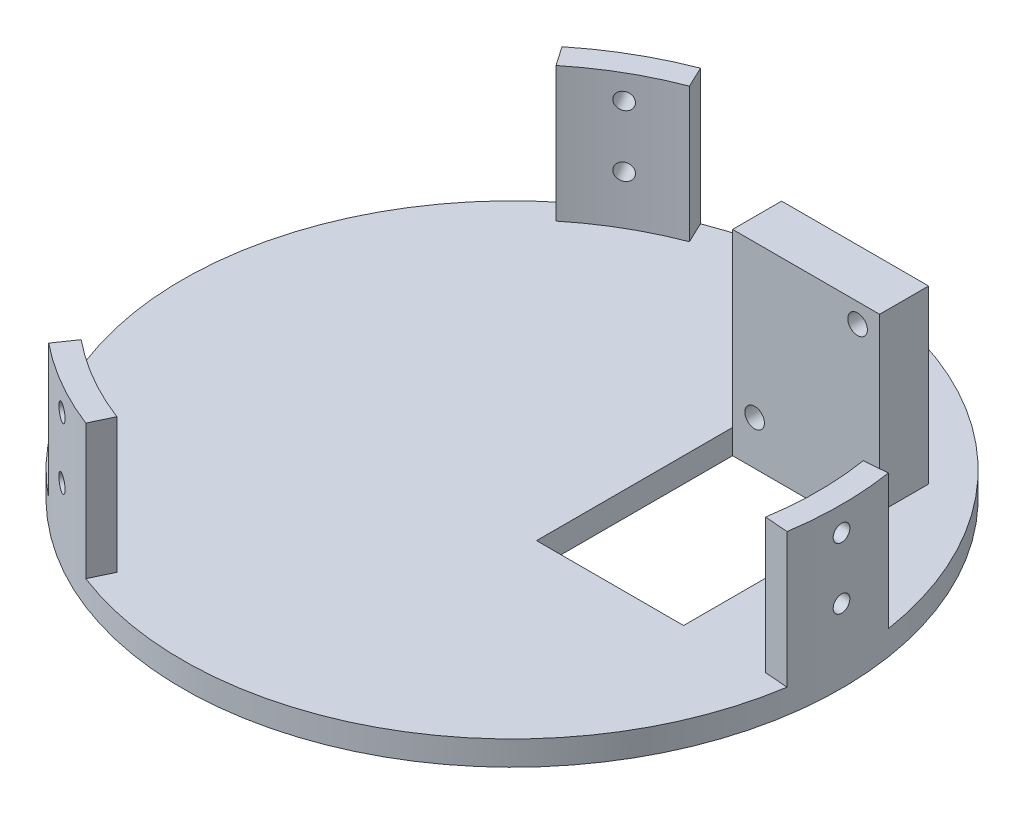
SolidWorks part; units mm, degrees
material "6061-T6 (SS)"
ref_plane "Front" through (0, 0, 0) normal (0, 0, 1) x (1, 0, 0)
ref_plane "Top" through (0, 0, 0) normal (0, 1, 0) x (1, 0, 0)
ref_plane "Right" through (0, 0, 0) normal (1, 0, 0) x (0, 0, -1)
sketch "Sketch1" plane through (0, 0, 0) normal (0, 1, 0) x (1, 0, 0)
  line L1 (0, 0) -> (127.635, 0)
  line L2 (0, 0) -> (0, 127.635)
  line L3 (0, 127.635) -> (127.635, 127.635)
  line L4 (127.635, 0) -> (127.635, 127.635)
  dimension "D1" = 127.635
  dimension "D2" = 127.635
extrude "Main Plate" add sketch "Sketch1" along normal blind 6.35
sketch "Sketch9" plane through (0, 6.35, 0) normal (0, 1, 0) x (1, 0, 0)
  circle A0 centre (63.8175, 63.8175) radius 85.725
  dimension "D1" = 171.45
extrude "Boss-Extrude1" add sketch "Sketch9" against normal up to surface (6.35 mm away) contours A0 up to face at (63.8175, 0, -63.8175)
sketch "Sketch10" plane through (0, 6.35, 0) normal (0, 1, 0) x (1, 0, 0)
  circle A0 centre (63.8175, 63.8175) radius 95.25
  circle A1 centre (63.8175, 63.8175) radius 85.4075
  dimension "D1" = 170.815
  dimension "D2" = 190.5
extrude "Cut-Extrude1" cut sketch "Sketch10" against normal blind 167.64 contours A0 | A1
sketch "Sketch14" plane through (0, 6.35, 0) normal (0, 1, 0) x (1, 0, 0)
  line L0 (201.1692, 63.8175) -> (-73.4523, 63.8175) construction
ref_plane "Plane1" through (0, 0, -63.8175) normal (0, 0, -1) x (-1, 0, 0)
ref_plane "Plane3" through (0, 3.175, 0) normal (0, 1, 0) x (1, 0, 0)
ref_plane "Plane2" through (-21.59, 0, 0) normal (-1, 0, 0) x (0, 0, 1)
sketch "Sketch18" plane through (0, 3.175, 0) normal (0, 1, 0) x (1, 0, 0)
  circle A0 centre (63.8175, 63.8175) radius 85.4075
  circle A1 centre (63.8175, 63.8175) radius 79.375
  circle A4 centre (63.8175, 63.8175) radius 85.4075 construction
  dimension "D1" = 158.75
extrude "Boss-Extrude2" add sketch "Sketch18" along normal blind 38.1
sketch "Sketch20" plane through (0, 6.35, 0) normal (0, 1, 0) x (1, 0, 0)
  line L0 (63.8175, 143.1925) -> (63.8175, -15.5575) construction
  line L1 (-15.5575, 63.8175) -> (143.1925, 63.8175) construction
  line L2 (63.8175, 63.8175) -> (-15.5575, -73.664) construction
  circle A0 centre (63.8175, 63.8175) radius 79.375 construction
  dimension "D1" = 30
ref_plane "Plane5" through (-15.5575, 6.35, 73.664) normal (-0.5, 0, 0.866) x (0.866, 0, 0.5)
sketch "Sketch15" plane through (166.2216, -6.35, 178.6143) normal (0.5, 0, -0.866) x (-0.866, 0, -0.5)
  line L3 (289.2754, 47.625) -> (130.5254, 47.625) construction
  circle A0 centre (209.9004, 25.4) radius 2.159
  circle A1 centre (209.9004, 41.275) radius 2.159
  dimension "D1" = 4.318
  dimension "D2" = 15.875
  dimension "D3" = 4.318
  dimension "D6" = 6.35
extrude "Cut-Extrude3" cut sketch "Sketch15" along normal blind 88.9
pattern_circular "CirPattern1" count 3 over 360 about axis through (63.8175, -161.29, -63.8175) along (0, 1, 0) of "Cut-Extrude3" reverse direction yes
ref_plane "Plane4" through (63.8175, 0, 0) normal (-1, 0, 0) x (0, 0, 1)
sketch "Sketch23" plane through (0, 6.35, 0) normal (0, 1, 0) x (1, 0, 0)
  line L0 (13.6787, 125.352) -> (7.5523, 134.2379)
  line L1 (15.1867, 11.8815) -> (13.6787, 2.283) construction
  line L3 (-15.5575, 63.8175) -> (143.1925, 63.8175) construction
  line L4 (63.8175, 143.1925) -> (63.8175, -15.5575) construction
  line L5 (-15.5575, 63.8175) -> (143.1925, 63.8175)
  line L6 (63.8175, 143.1925) -> (63.8175, -15.5575)
  line L7 (13.6787, 2.283) -> (6.9592, -7.4631)
  line L8 (-19.2671, 125.3206) -> (-48.797, 60.3978)
  line L9 (-48.797, 60.3978) -> (-9.8843, 7.0525)
  line L10 (-9.8843, 7.0525) -> (6.9592, -7.4631)
  line L11 (24.1345, -4.9259) -> (13.6787, 2.283) construction
  line L14 (7.5523, 134.2379) -> (-19.2671, 125.3206)
  line L15 (24.1345, 132.5609) -> (13.6787, 125.352) construction
  line L28 (63.8175, 63.8175) -> (24.1345, -4.9259) construction
  line L29 (63.8175, 63.8175) -> (24.1345, 132.5609) construction
  line L30 (142.1773, 76.4717) -> (152.9359, 77.3344)
  line L31 (152.9359, 77.3344) -> (158.6231, 105.0193)
  line L32 (158.6231, 105.0193) -> (117.1632, 163.0543)
  line L33 (117.1632, 163.0543) -> (51.5085, 156.0277)
  line L34 (51.5085, 156.0277) -> (30.5159, 148.6985)
  line L35 (35.5964, 138.0062) -> (30.5159, 148.6985)
  line L36 (35.5964, -10.3712) -> (30.9643, -20.1198)
  line L37 (30.9643, -20.1198) -> (52.0965, -38.8874)
  line L38 (52.0965, -38.8874) -> (123.0863, -31.9996)
  line L39 (123.0863, -31.9996) -> (149.8284, 28.3723)
  line L40 (149.8284, 28.3723) -> (153.9775, 50.217)
  line L41 (142.1773, 51.1633) -> (153.9775, 50.217)
  circle A0 centre (63.8175, 63.8175) radius 79.375 construction
  arc A1 (13.6787, 2.283) -> (13.6787, 125.352) centre (63.8175, 63.8175) cw
  circle A3 centre (63.8175, 63.8175) radius 79.375
  arc A6 (35.5964, 138.0062) -> (142.1773, 76.4717) centre (63.8175, 63.8175) cw
  arc A7 (142.1773, 51.1633) -> (35.5964, -10.3712) centre (63.8175, 63.8175) cw
  circle A9 centre (63.8175, 63.8175) radius 79.375
  circle M15 centre (63.8175, 63.8175) radius 79.375
  dimension "D1" = 79.375
  dimension "D2" = 0
  dimension "D3" = 12.7
  dimension "D4" = 90
  dimension "D5" = 12.7
  dimension "D6" = 90
  dimension "D8" = 60.004
  dimension "D9" = 60.004
  dimension "D7" = 3
extrude "Cut-Extrude6" cut sketch "Sketch23" along normal blind 111.6 contours L9 L10 L7 L8 M15 | L34 L35 A6 L30 L31 L32 L33 | L40 L41 A7 L36 L37 L38 L39 region at (-18.2379, 6.35, -69.3048)
sketch "Sketch24" plane through (0, 6.35, 0) normal (0, 1, 0) x (1, 0, 0)
  line L1 (82.8675, 101.9175) -> (120.9675, 101.9175)
  line L2 (82.8675, 101.9175) -> (82.8675, 51.1175)
  line L3 (82.8675, 51.1175) -> (120.9675, 51.1175)
  line L4 (120.9675, 101.9175) -> (120.9675, 51.1175)
  line L5 (82.8675, 101.9175) -> (120.9675, 51.1175) construction
  line L6 (82.8675, 51.1175) -> (120.9675, 101.9175) construction
  arc A0 (148.2085, 76.9553) -> (32.9997, 143.4712) centre (63.8175, 63.8175) ccw construction
  arc A1 (148.2085, 76.9553) -> (32.9997, 143.4712) centre (63.8175, 63.8175) ccw
  point P0 (101.9175, 76.5175)
  dimension "D1" = 50.8
  dimension "D2" = 38.1
  dimension "D3" = 12.7
  dimension "D4" = 38.1
extrude "Cut-Extrude7" cut sketch "Sketch24" against normal through all contours L4 L1 L2 L3 region at (101.9175, 6.35, -76.5175)
sketch "Sketch25" plane through (0, 6.35, 0) normal (0, 1, 0) x (1, 0, 0)
  line L1 (82.8675, 114.6175) -> (120.9675, 114.6175)
  line L2 (82.8675, 114.6175) -> (82.8675, 101.9175)
  line L3 (82.8675, 101.9175) -> (120.9675, 101.9175)
  line L4 (120.9675, 114.6175) -> (120.9675, 101.9175)
  line L5 (82.8675, 114.6175) -> (120.9675, 101.9175) construction
  line L6 (82.8675, 101.9175) -> (120.9675, 114.6175) construction
  point P0 (101.9175, 108.2675)
  dimension "D1" = 12.7
extrude "Boss-Extrude3" add sketch "Sketch25" along normal blind 44.45
sketch "Sketch26" plane through (0, 0, -101.9175) normal (0, 0, 1) x (1, 0, 0)
  line L1 (82.8675, 50.8) -> (120.9675, 50.8) construction
  line L2 (120.9675, 50.8) -> (120.9675, 6.35) construction
  circle A0 centre (115.2525, 45.72) radius 2.54
  circle A1 centre (88.5825, 11.43) radius 2.54
  dimension "D1" = 5.08
  dimension "D2" = 5.715
  dimension "D3" = 34.29
  dimension "D4" = 5.08
  dimension "D5" = 26.67
extrude "Cut-Extrude8" cut sketch "Sketch26" against normal blind 44.45
